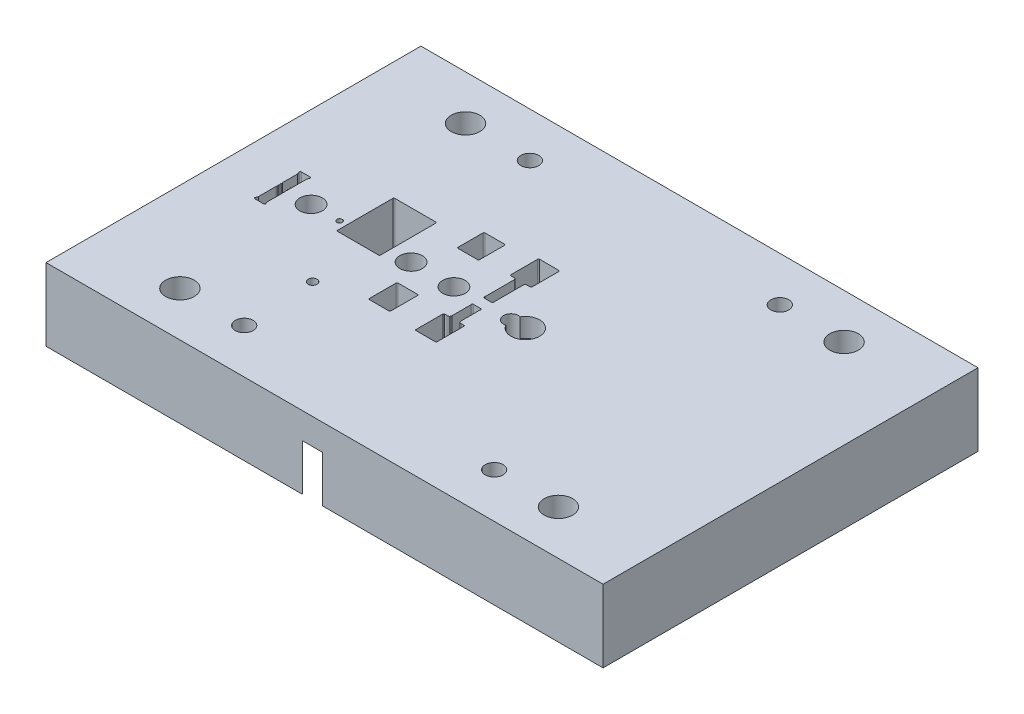
SolidWorks part; units mm, degrees
ref_plane "Front" through (0, 0, 0) normal (0, 0, 1) x (1, 0, 0)
ref_plane "Top" through (0, 0, 0) normal (0, 1, 0) x (1, 0, 0)
ref_plane "Right" through (0, 0, 0) normal (1, 0, 0) x (0, 0, -1)
sketch "Sketch1" plane through (0, 0, 0) normal (0, 0, 1) x (1, 0, 0)
  line L1 (-78, 0) -> (78, 0)
  line L2 (-78, 0) -> (-78, 20.3)
  line L3 (-78, 20.3) -> (78, 20.3)
  line L4 (78, 0) -> (78, 20.3)
  dimension "D1" = 78
  dimension "D2" = 20.3
  dimension "D3" = 78
extrude "Extrude1" add sketch "Sketch1" along normal mid plane 105
hole_wizard "M6 Tapped Hole1" positions "Sketch3" profile "Sketch2" tap size "M6" standard "ISO" end condition through all
sketch "Sketch3" plane through (0, 20.3, 0) normal (0, 1, 0) x (-1, 0, 0)
  point P1 (35, -40)
  point P4 (-35, -40)
  point P13 (-35, 40)
  point P16 (35, 40)
sketch "Sketch2" plane through (-35, 20.3, -40) normal (1, 0, 0) x (0, 0, 1)
  line L0 (0, 0) -> (0, 20.3)
  line L1 (0, 20.3) -> (2.5, 20.3)
  line L2 (2.5, 20.3) -> (2.5, 0)
  line L5 (2.5, 0) -> (0, 0)
  line L11 (0, -6.35) -> (0, 107.95) construction
  dimension "Thru Tap Drill Dia." = 5
  dimension "Thru Tap Drill Depth" = 20.3
cosmetic thread "Hole Thread1" parameters "D2"=6
cosmetic thread "Hole Thread2" parameters "D2"=6
cosmetic thread "Hole Thread5" parameters "D2"=6
cosmetic thread "Hole Thread6" parameters "D2"=6
hole_wizard "Hole1" positions "Sketch5" profile "Sketch4" legacy end condition through all
sketch "Sketch5" plane through (0, 20.3, 0) normal (0, 1, 0) x (-1, 0, 0)
  point P1 (53, -40)
  point P4 (53, 40)
  point P7 (-53, -40)
  point P10 (-53, 40)
sketch "Sketch4" plane through (-53, 20.3, -40) normal (1, 0, 0) x (0, 0, 1)
  line L0 (0, 0) -> (0, 20.3)
  line L1 (0, 20.3) -> (4, 20.3)
  line L2 (4, 20.3) -> (4, 0)
  line L3 (4, 0) -> (0, 0)
  line L4 (0, 110) -> (0, -10) construction
  dimension "Diameter" = 8
  dimension "Depth" = 20.3
hole_wizard "Hole2" positions "Sketch7" profile "Sketch6" legacy
sketch "Sketch7" plane through (0, 0, 0) normal (0, -1, 0) x (1, 0, 0)
  point P0 (14, 14.65)
  point P3 (5, 12.15)
  point P6 (5, -12.1677)
  point P8 (14, -14.65)
  point P11 (35, -12.15)
  point P14 (35, 12.15)
  point P17 (44, 14.65)
  point P20 (44, -14.65)
sketch "Sketch6" plane through (14, 0, 14.65) normal (1, 0, 0) x (0, 0, -1)
  line L0 (0, 0) -> (0, 4.4)
  line L1 (0, 4.4) -> (3.5, 4.4)
  line L2 (3.5, 4.4) -> (3.5, 0)
  line L3 (3.5, 0) -> (0, 0)
  line L4 (0, 110) -> (0, -10) construction
  dimension "Diameter" = 7
  dimension "Depth" = 4.4
sketch "Sketch8" plane through (0, 0, 0) normal (0, -1, 0) x (1, 0, 0)
  line L0 (-78, 52.5) -> (-78, -52.5) construction
  line L1 (-78, 23) -> (-49, 23)
  line L2 (-78, 23) -> (-78, 5)
  line L3 (-78, 5) -> (-49, 5)
  line L4 (-46, 20) -> (-46, 8)
  line L5 (-75.2525, 6) -> (-50.7475, 6) construction
  line L6 (-78, -1) -> (-49, -1)
  line L7 (-78, -1) -> (-78, -21)
  line L8 (-78, -21) -> (-49, -21)
  line L9 (-46, -4) -> (-46, -18)
  line L10 (-78, 22) -> (-48, 22) construction
  line L11 (-76.6263, -2) -> (-49.3737, -2) construction
  line L13 (-78, -20) -> (-48, -20) construction
  line L14 (-48, 11) -> (-48, 22) construction
  arc A0 (-49, -21) -> (-46, -18) centre (-49, -18) ccw
  arc A1 (-49, -1) -> (-46, -4) centre (-49, -4) cw
  arc A2 (-49, 5) -> (-46, 8) centre (-49, 8) ccw
  arc A3 (-49, 23) -> (-46, 20) centre (-49, 20) cw
  dimension "D6" = 3
  dimension "D1" = 1
  dimension "D2" = 1
  dimension "D3" = 1
  dimension "D4" = 1
  dimension "D5" = 2
extrude "Cut-Extrude1" cut sketch "Sketch8" against normal blind 5
sketch "Sketch9" plane through (0, 20.3, 0) normal (0, 1, 0) x (1, 0, 0)
  line L0 (-9.965, 17.15) -> (-9.965, 9.65)
  line L1 (-9.7, 9.385) -> (-8.5894, 9.385)
  line L2 (-8.3917, 9.2771) -> (-8.3123, 9.1537)
  line L3 (-8.275, 9.0266) -> (-8.275, 0.7046)
  line L4 (-18.25, -8.1954) -> (-23.75, -8.1954)
  line L5 (-24, -8.4454) -> (-24, -15.9454)
  line L6 (-23.75, -16.1954) -> (-18.25, -16.1954)
  line L7 (-18, -15.9454) -> (-18, -8.4454)
  line L8 (-18.25, -8.1954) -> (-23.75, -8.1954) construction
  line L9 (-24, -8.4454) -> (-24, -15.9454) construction
  line L10 (-23.75, -16.1954) -> (-18.25, -16.1954) construction
  line L11 (-18, -15.9454) -> (-18, -8.4454) construction
  line L12 (-24, 15.9) -> (-24, 8.9)
  line L13 (-23.75, 8.65) -> (-18.25, 8.65)
  line L14 (-18, 8.9) -> (-18, 15.9)
  line L15 (-18.25, 16.15) -> (-23.75, 16.15)
  line L16 (-24, 15.9) -> (-24, 8.9) construction
  line L17 (-23.75, 8.65) -> (-18.25, 8.65) construction
  line L18 (-18, 8.9) -> (-18, 15.9) construction
  line L19 (-18.25, 16.15) -> (-23.75, 16.15) construction
  line L20 (-33.25, 11.9046) -> (-44.75, 11.9046)
  line L21 (-33, -3.8454) -> (-33, 11.6546)
  line L22 (-44.75, -4.0954) -> (-33.25, -4.0954)
  line L23 (-45, 11.6546) -> (-45, -3.8454)
  line L24 (-33.25, 11.9046) -> (-44.75, 11.9046) construction
  line L25 (-33, -3.8454) -> (-33, 11.6546) construction
  line L26 (-44.75, -4.0954) -> (-33.25, -4.0954) construction
  line L27 (-45, 11.6546) -> (-45, -3.8454) construction
  line L28 (-8.2892, 0.6243) -> (-8.299, 0.5972)
  line L29 (-8.05, 0.2416) -> (-5.95, 0.2416)
  line L30 (-63, -1.2694) -> (-60.1263, -1.2694) construction
  line L31 (-61.75, -6.7884) -> (-61.5151, -7.4339) construction
  line L32 (-64.25, -6.7884) -> (-64.4849, -7.4339) construction
  line L33 (-61.735, -6.7858) -> (-61.501, -7.4288)
  line L34 (-61.75, -7.7844) -> (-64.25, -7.7844)
  line L35 (-64.265, -6.7858) -> (-64.499, -7.4288)
  line L36 (-9, -9.1754) -> (-9.7, -9.1754)
  line L37 (-9.95, -9.4254) -> (-9.95, -16.9254)
  line L38 (-9.7, -17.1754) -> (-4.3, -17.1754)
  line L39 (-4.05, -16.9254) -> (-4.05, -9.4254)
  line L40 (-4.3, -9.1754) -> (-5, -9.1754)
  line L41 (-5.6073, -8.9669) -> (-5.7285, -8.582)
  line L42 (-5.74, -8.5069) -> (-5.74, -3.2709)
  line L43 (-5.7249, -3.1854) -> (-5.7051, -3.1309)
  line L44 (-5.94, -2.7954) -> (-8.06, -2.7954)
  line L45 (-8.2949, -3.1309) -> (-8.2751, -3.1854)
  line L46 (-8.26, -3.2709) -> (-8.26, -8.5069)
  line L47 (-8.2715, -8.582) -> (-8.3927, -8.9669)
  line L48 (-9, -9.1754) -> (-9.7, -9.1754) construction
  line L49 (-9.95, -9.4254) -> (-9.95, -16.9254) construction
  line L50 (-9.7, -17.1754) -> (-4.3, -17.1754) construction
  line L51 (-4.05, -16.9254) -> (-4.05, -9.4254) construction
  line L52 (-4.3, -9.1754) -> (-5, -9.1754) construction
  line L53 (-5.6073, -8.9669) -> (-5.7285, -8.582) construction
  line L54 (-5.74, -8.5069) -> (-5.74, -3.2709) construction
  line L55 (-5.7249, -3.1854) -> (-5.7051, -3.1309) construction
  line L56 (-5.94, -2.7954) -> (-8.06, -2.7954) construction
  line L57 (-8.2949, -3.1309) -> (-8.2751, -3.1854) construction
  line L58 (-8.26, -3.2709) -> (-8.26, -8.5069) construction
  line L59 (-8.2715, -8.582) -> (-8.3927, -8.9669) construction
  line L60 (-9.95, 17.15) -> (-9.95, 9.65)
  line L61 (-9.7, 9.4) -> (-8.5894, 9.4)
  line L62 (-8.3791, 9.2852) -> (-8.2997, 9.1618)
  line L63 (-8.26, 9.0266) -> (-8.26, 0.7046)
  line L64 (-8.2751, 0.6191) -> (-8.2849, 0.5921)
  line L65 (-8.05, 0.2566) -> (-5.95, 0.2566)
  line L66 (-5.7151, 0.5921) -> (-5.7249, 0.6191)
  line L67 (-5.74, 0.7046) -> (-5.74, 9.0266)
  line L68 (-5.7003, 9.1618) -> (-5.6209, 9.2852)
  line L69 (-5.4106, 9.4) -> (-4.3, 9.4)
  line L70 (-4.05, 9.65) -> (-4.05, 17.15)
  line L71 (-4.3, 17.4) -> (-9.7, 17.4)
  line L72 (-9.95, 17.15) -> (-9.95, 9.65) construction
  line L73 (-9.7, 9.4) -> (-8.5894, 9.4) construction
  line L74 (-8.3791, 9.2852) -> (-8.2997, 9.1618) construction
  line L75 (-8.26, 9.0266) -> (-8.26, 0.7046) construction
  line L76 (-8.2751, 0.6191) -> (-8.2849, 0.5921) construction
  line L77 (-8.05, 0.2566) -> (-5.95, 0.2566) construction
  line L78 (-5.7151, 0.5921) -> (-5.7249, 0.6191) construction
  line L79 (-5.74, 0.7046) -> (-5.74, 9.0266) construction
  line L80 (-5.7003, 9.1618) -> (-5.6209, 9.2852) construction
  line L81 (-5.4106, 9.4) -> (-4.3, 9.4) construction
  line L82 (-4.05, 9.65) -> (-4.05, 17.15) construction
  line L83 (-4.3, 17.4) -> (-9.7, 17.4) construction
  line L84 (-64.265, -1.7954) -> (-64.265, -6.7858)
  line L85 (-64.265, 4.247) -> (-64.265, 0.0046)
  line L86 (-64.265, 4.247) -> (-64.499, 4.89)
  line L87 (-64.25, 5.2456) -> (-61.75, 5.2456)
  line L88 (-61.735, 4.247) -> (-61.501, 4.89)
  line L89 (-61.735, 0.0046) -> (-61.735, 4.247)
  line L90 (-5.701, 0.5972) -> (-5.7108, 0.6243)
  line L91 (-5.725, 0.7046) -> (-5.725, 9.0266)
  line L92 (-5.6877, 9.1537) -> (-5.6083, 9.2771)
  line L93 (-5.4106, 9.385) -> (-4.3, 9.385)
  line L94 (-4.035, 9.65) -> (-4.035, 17.15)
  line L95 (-4.3, 17.415) -> (-9.7, 17.415)
  line L96 (-61.735, -6.7858) -> (-61.735, -1.7954)
  line L114 (-64.25, 7.2306) -> (-64.25, 0.0046) construction
  line L115 (-61.75, 0.0046) -> (-61.75, 7.2306) construction
  line L116 (-64.25, -1.7954) -> (-64.25, -9.7694) construction
  line L117 (-61.75, -9.7694) -> (-61.75, -1.7954) construction
  line L118 (-61.75, -7.7694) -> (-64.25, -7.7694) construction
  line L119 (-64.25, 5.2306) -> (-61.75, 5.2306) construction
  line L120 (-64.25, 4.2497) -> (-64.25, 0.0046) construction
  line L121 (-61.75, 0.0046) -> (-61.75, 4.2497) construction
  line L122 (-64.25, -1.7954) -> (-64.25, -6.7884) construction
  line L123 (-61.75, -6.7884) -> (-61.75, -1.7954) construction
  line L124 (-61.75, -7.7694) -> (-64.25, -7.7694) construction
  line L125 (-64.25, 5.2306) -> (-61.75, 5.2306) construction
  line L126 (-64.25, 4.2497) -> (-64.4849, 4.8951) construction
  line L127 (-64.25, 3.4217) -> (-61.75, 3.4217) construction
  line L128 (-63, 3.4217) -> (-63, 4.4835) construction
  line L129 (-61.75, 4.2497) -> (-61.5151, 4.8951) construction
  line L130 (-63, -7.7694) -> (-63, 5.2306) construction
  line L138 (-9, -9.1604) -> (-9.7, -9.1604)
  line L139 (-9.965, -9.4254) -> (-9.965, -16.9254)
  line L140 (-9.7, -17.1904) -> (-4.3, -17.1904)
  line L141 (-4.035, -16.9254) -> (-4.035, -9.4254)
  line L142 (-4.3, -9.1604) -> (-5, -9.1604)
  line L143 (-5.593, -8.9624) -> (-5.7142, -8.5775)
  line L144 (-5.725, -8.5069) -> (-5.725, -3.2709)
  line L145 (-5.7108, -3.1905) -> (-5.691, -3.136)
  line L146 (-5.94, -2.7804) -> (-8.06, -2.7804)
  line L147 (-8.309, -3.136) -> (-8.2892, -3.1905)
  line L148 (-8.275, -3.2709) -> (-8.275, -8.5069)
  line L149 (-8.2858, -8.5775) -> (-8.407, -8.9624)
  line L150 (-24.015, 15.9) -> (-24.015, 8.9)
  line L151 (-23.75, 8.635) -> (-18.25, 8.635)
  line L152 (-17.985, 8.9) -> (-17.985, 15.9)
  line L153 (-18.25, 16.165) -> (-23.75, 16.165)
  line L154 (-18.25, -8.1804) -> (-23.75, -8.1804)
  line L155 (-24.015, -8.4454) -> (-24.015, -15.9454)
  line L156 (-23.75, -16.2104) -> (-18.25, -16.2104)
  line L157 (-17.985, -15.9454) -> (-17.985, -8.4454)
  line L158 (-33.25, 11.9196) -> (-44.75, 11.9196)
  line L159 (-45.015, 11.6546) -> (-45.015, -3.8454)
  line L160 (-44.75, -4.1104) -> (-33.25, -4.1104)
  line L161 (-32.985, -3.8454) -> (-32.985, 11.6546)
  arc A0 (-9.965, 9.65) -> (-9.7, 9.385) centre (-9.7, 9.65) ccw
  arc A1 (-8.3917, 9.2771) -> (-8.5894, 9.385) centre (-8.5894, 9.15) ccw
  arc A2 (-8.275, 9.0266) -> (-8.3123, 9.1537) centre (-8.51, 9.0266) ccw
  arc A3 (-8.2892, 0.6243) -> (-8.275, 0.7046) centre (-8.51, 0.7046) ccw
  arc A4 (-23.75, -8.1954) -> (-24, -8.4454) centre (-23.75, -8.4454) ccw
  arc A5 (-24, -15.9454) -> (-23.75, -16.1954) centre (-23.75, -15.9454) ccw
  arc A6 (-18.25, -16.1954) -> (-18, -15.9454) centre (-18.25, -15.9454) ccw
  arc A7 (-18, -8.4454) -> (-18.25, -8.1954) centre (-18.25, -8.4454) ccw
  arc A8 (-23.75, -8.1954) -> (-24, -8.4454) centre (-23.75, -8.4454) ccw construction
  arc A9 (-24, -15.9454) -> (-23.75, -16.1954) centre (-23.75, -15.9454) ccw construction
  arc A10 (-18.25, -16.1954) -> (-18, -15.9454) centre (-18.25, -15.9454) ccw construction
  arc A11 (-18, -8.4454) -> (-18.25, -8.1954) centre (-18.25, -8.4454) ccw construction
  arc A12 (-24, 8.9) -> (-23.75, 8.65) centre (-23.75, 8.9) ccw
  arc A13 (-18.25, 8.65) -> (-18, 8.9) centre (-18.25, 8.9) ccw
  arc A14 (-18, 15.9) -> (-18.25, 16.15) centre (-18.25, 15.9) ccw
  arc A15 (-23.75, 16.15) -> (-24, 15.9) centre (-23.75, 15.9) ccw
  arc A16 (-24, 8.9) -> (-23.75, 8.65) centre (-23.75, 8.9) ccw construction
  arc A17 (-18.25, 8.65) -> (-18, 8.9) centre (-18.25, 8.9) ccw construction
  arc A18 (-18, 15.9) -> (-18.25, 16.15) centre (-18.25, 15.9) ccw construction
  arc A19 (-23.75, 16.15) -> (-24, 15.9) centre (-23.75, 15.9) ccw construction
  arc A20 (-33, 11.6546) -> (-33.25, 11.9046) centre (-33.25, 11.6546) ccw
  arc A21 (-33.25, -4.0954) -> (-33, -3.8454) centre (-33.25, -3.8454) ccw
  arc A22 (-45, -3.8454) -> (-44.75, -4.0954) centre (-44.75, -3.8454) ccw
  arc A23 (-44.75, 11.9046) -> (-45, 11.6546) centre (-44.75, 11.6546) ccw
  arc A24 (-33, 11.6546) -> (-33.25, 11.9046) centre (-33.25, 11.6546) ccw construction
  arc A25 (-33.25, -4.0954) -> (-33, -3.8454) centre (-33.25, -3.8454) ccw construction
  arc A26 (-45, -3.8454) -> (-44.75, -4.0954) centre (-44.75, -3.8454) ccw construction
  arc A27 (-44.75, 11.9046) -> (-45, 11.6546) centre (-44.75, 11.6546) ccw construction
  arc A28 (-8.299, 0.5972) -> (-8.05, 0.2416) centre (-8.05, 0.5066) ccw
  arc A29 (-5.95, 0.2416) -> (-5.701, 0.5972) centre (-5.95, 0.5066) ccw
  arc A30 (-5.725, 0.7046) -> (-5.7108, 0.6243) centre (-5.49, 0.7046) ccw
  arc A31 (-5.6877, 9.1537) -> (-5.725, 9.0266) centre (-5.49, 9.0266) ccw
  arc A32 (-5.4106, 9.385) -> (-5.6083, 9.2771) centre (-5.4106, 9.15) ccw
  arc A33 (-4.3, 9.385) -> (-4.035, 9.65) centre (-4.3, 9.65) ccw
  arc A34 (-4.035, 17.15) -> (-4.3, 17.415) centre (-4.3, 17.15) ccw
  arc A35 (-9.7, 17.415) -> (-9.965, 17.15) centre (-9.7, 17.15) ccw
  arc A36 (-9.95, 9.65) -> (-9.7, 9.4) centre (-9.7, 9.65) ccw
  arc A37 (-8.3791, 9.2852) -> (-8.5894, 9.4) centre (-8.5894, 9.15) ccw
  arc A38 (-8.26, 9.0266) -> (-8.2997, 9.1618) centre (-8.51, 9.0266) ccw
  arc A39 (-8.2751, 0.6191) -> (-8.26, 0.7046) centre (-8.51, 0.7046) ccw
  arc A40 (-8.5194, -9.0963) -> (-8.4688, -9.0707) centre (-8.5835, -8.9068) ccw
  arc A41 (-9, -9.1754) -> (-8.5194, -9.0963) centre (-9, -7.6754) ccw
  arc A42 (-9.7, -9.1754) -> (-9.95, -9.4254) centre (-9.7, -9.4254) ccw
  arc A43 (-9.95, -16.9254) -> (-9.7, -17.1754) centre (-9.7, -16.9254) ccw
  arc A44 (-4.3, -17.1754) -> (-4.05, -16.9254) centre (-4.3, -16.9254) ccw
  arc A45 (-4.05, -9.4254) -> (-4.3, -9.1754) centre (-4.3, -9.4254) ccw
  arc A46 (-5.4806, -9.0963) -> (-5, -9.1754) centre (-5, -7.6754) ccw
  arc A47 (-5.5312, -9.0707) -> (-5.4806, -9.0963) centre (-5.4165, -8.9068) ccw
  arc A48 (-5.6073, -8.9669) -> (-5.5312, -9.0707) centre (-5.4165, -8.9068) ccw
  arc A49 (-5.74, -8.5069) -> (-5.7285, -8.582) centre (-5.49, -8.5069) ccw
  arc A50 (-5.7249, -3.1854) -> (-5.74, -3.2709) centre (-5.49, -3.2709) ccw
  arc A51 (-5.7051, -3.1309) -> (-5.94, -2.7954) centre (-5.94, -3.0454) ccw
  arc A52 (-8.06, -2.7954) -> (-8.2949, -3.1309) centre (-8.06, -3.0454) ccw
  arc A53 (-8.26, -3.2709) -> (-8.2751, -3.1854) centre (-8.51, -3.2709) ccw
  arc A54 (-8.2715, -8.582) -> (-8.26, -8.5069) centre (-8.51, -8.5069) ccw
  arc A55 (-8.4688, -9.0707) -> (-8.3927, -8.9669) centre (-8.5835, -8.9068) ccw
  arc A56 (-8.5194, -9.0963) -> (-8.4688, -9.0707) centre (-8.5835, -8.9068) ccw construction
  arc A57 (-9, -9.1754) -> (-8.5194, -9.0963) centre (-9, -7.6754) ccw construction
  arc A58 (-9.7, -9.1754) -> (-9.95, -9.4254) centre (-9.7, -9.4254) ccw construction
  arc A59 (-9.95, -16.9254) -> (-9.7, -17.1754) centre (-9.7, -16.9254) ccw construction
  arc A60 (-4.3, -17.1754) -> (-4.05, -16.9254) centre (-4.3, -16.9254) ccw construction
  arc A61 (-4.05, -9.4254) -> (-4.3, -9.1754) centre (-4.3, -9.4254) ccw construction
  arc A62 (-5.4806, -9.0963) -> (-5, -9.1754) centre (-5, -7.6754) ccw construction
  arc A63 (-5.5312, -9.0707) -> (-5.4806, -9.0963) centre (-5.4165, -8.9068) ccw construction
  arc A64 (-5.6073, -8.9669) -> (-5.5312, -9.0707) centre (-5.4165, -8.9068) ccw construction
  arc A65 (-5.74, -8.5069) -> (-5.7285, -8.582) centre (-5.49, -8.5069) ccw construction
  arc A66 (-5.7249, -3.1854) -> (-5.74, -3.2709) centre (-5.49, -3.2709) ccw construction
  arc A67 (-5.7051, -3.1309) -> (-5.94, -2.7954) centre (-5.94, -3.0454) ccw construction
  arc A68 (-8.06, -2.7954) -> (-8.2949, -3.1309) centre (-8.06, -3.0454) ccw construction
  arc A69 (-8.26, -3.2709) -> (-8.2751, -3.1854) centre (-8.51, -3.2709) ccw construction
  arc A70 (-8.2715, -8.582) -> (-8.26, -8.5069) centre (-8.51, -8.5069) ccw construction
  arc A71 (-8.4688, -9.0707) -> (-8.3927, -8.9669) centre (-8.5835, -8.9068) ccw construction
  arc A72 (-8.2849, 0.5921) -> (-8.05, 0.2566) centre (-8.05, 0.5066) ccw
  arc A73 (-5.95, 0.2566) -> (-5.7151, 0.5921) centre (-5.95, 0.5066) ccw
  arc A74 (-5.74, 0.7046) -> (-5.7249, 0.6191) centre (-5.49, 0.7046) ccw
  arc A75 (-5.7003, 9.1618) -> (-5.74, 9.0266) centre (-5.49, 9.0266) ccw
  arc A76 (-5.4106, 9.4) -> (-5.6209, 9.2852) centre (-5.4106, 9.15) ccw
  arc A77 (-4.3, 9.4) -> (-4.05, 9.65) centre (-4.3, 9.65) ccw
  arc A78 (-4.05, 17.15) -> (-4.3, 17.4) centre (-4.3, 17.15) ccw
  arc A79 (-9.7, 17.4) -> (-9.95, 17.15) centre (-9.7, 17.15) ccw
  arc A80 (-9.95, 9.65) -> (-9.7, 9.4) centre (-9.7, 9.65) ccw construction
  arc A81 (-8.3791, 9.2852) -> (-8.5894, 9.4) centre (-8.5894, 9.15) ccw construction
  arc A82 (-8.26, 9.0266) -> (-8.2997, 9.1618) centre (-8.51, 9.0266) ccw construction
  arc A83 (-8.2751, 0.6191) -> (-8.26, 0.7046) centre (-8.51, 0.7046) ccw construction
  arc A84 (-8.2849, 0.5921) -> (-8.05, 0.2566) centre (-8.05, 0.5066) ccw construction
  arc A85 (-5.95, 0.2566) -> (-5.7151, 0.5921) centre (-5.95, 0.5066) ccw construction
  arc A86 (-5.74, 0.7046) -> (-5.7249, 0.6191) centre (-5.49, 0.7046) ccw construction
  arc A87 (-5.7003, 9.1618) -> (-5.74, 9.0266) centre (-5.49, 9.0266) ccw construction
  arc A88 (-5.4106, 9.4) -> (-5.6209, 9.2852) centre (-5.4106, 9.15) ccw construction
  arc A89 (-4.3, 9.4) -> (-4.05, 9.65) centre (-4.3, 9.65) ccw construction
  arc A90 (-4.05, 17.15) -> (-4.3, 17.4) centre (-4.3, 17.15) ccw construction
  arc A91 (-9.7, 17.4) -> (-9.95, 17.15) centre (-9.7, 17.15) ccw construction
  arc A92 (-61.5151, -7.4339) -> (-61.75, -7.7694) centre (-61.75, -7.5194) cw construction
  arc A93 (-64.4849, -7.4339) -> (-64.25, -7.7694) centre (-64.25, -7.5194) ccw construction
  arc A94 (-61.501, -7.4288) -> (-61.75, -7.7844) centre (-61.75, -7.5194) cw
  arc A95 (-64.499, -7.4288) -> (-64.25, -7.7844) centre (-64.25, -7.5194) ccw
  arc A96 (-64.212, -1.6364) -> (-64.265, -1.7954) centre (-64, -1.7954) ccw
  arc A97 (-64.212, -1.6364) -> (-64.212, -1.3544) centre (-64.4, -1.4954) ccw
  arc A98 (-64.212, -1.0364) -> (-64.212, -1.3544) centre (-64, -1.1954) ccw
  arc A99 (-64.212, -1.0364) -> (-64.212, -0.7544) centre (-64.4, -0.8954) ccw
  arc A100 (-64.212, -0.4364) -> (-64.212, -0.7544) centre (-64, -0.5954) ccw
  arc A101 (-64.212, -0.4364) -> (-64.212, -0.1544) centre (-64.4, -0.2954) ccw
  arc A102 (-64.265, 0.0046) -> (-64.212, -0.1544) centre (-64, 0.0046) ccw
  arc A103 (-64.499, 4.89) -> (-64.25, 5.2456) centre (-64.25, 4.9806) cw
  arc A104 (-61.501, 4.89) -> (-61.75, 5.2456) centre (-61.75, 4.9806) ccw
  arc A105 (-61.788, -0.1544) -> (-61.735, 0.0046) centre (-62, 0.0046) ccw
  arc A106 (-61.788, -0.1544) -> (-61.788, -0.4364) centre (-61.6, -0.2954) ccw
  arc A107 (-61.788, -0.7544) -> (-61.788, -0.4364) centre (-62, -0.5954) ccw
  arc A108 (-61.788, -0.7544) -> (-61.788, -1.0364) centre (-61.6, -0.8954) ccw
  arc A109 (-61.788, -1.3544) -> (-61.788, -1.0364) centre (-62, -1.1954) ccw
  arc A110 (-61.788, -1.3544) -> (-61.788, -1.6364) centre (-61.6, -1.4954) ccw
  arc A111 (-61.735, -1.7954) -> (-61.788, -1.6364) centre (-62, -1.7954) ccw
  arc A132 (-61.8, -0.1454) -> (-61.75, 0.0046) centre (-62, 0.0046) ccw construction
  arc A133 (-61.8, -0.1454) -> (-61.8, -0.4454) centre (-61.6, -0.2954) ccw construction
  arc A134 (-61.8, -0.7454) -> (-61.8, -0.4454) centre (-62, -0.5954) ccw construction
  arc A135 (-61.8, -0.7454) -> (-61.8, -1.0454) centre (-61.6, -0.8954) ccw construction
  arc A136 (-61.8, -1.3454) -> (-61.8, -1.0454) centre (-62, -1.1954) ccw construction
  arc A137 (-61.8, -1.3454) -> (-61.8, -1.6454) centre (-61.6, -1.4954) ccw construction
  arc A138 (-61.75, -1.7954) -> (-61.8, -1.6454) centre (-62, -1.7954) ccw construction
  arc A139 (-61.8, -0.1454) -> (-61.75, 0.0046) centre (-62, 0.0046) ccw construction
  arc A140 (-61.8, -0.1454) -> (-61.8, -0.4454) centre (-61.6, -0.2954) ccw construction
  arc A141 (-61.8, -0.7454) -> (-61.8, -0.4454) centre (-62, -0.5954) ccw construction
  arc A142 (-61.8, -0.7454) -> (-61.8, -1.0454) centre (-61.6, -0.8954) ccw construction
  arc A143 (-61.8, -1.3454) -> (-61.8, -1.0454) centre (-62, -1.1954) ccw construction
  arc A144 (-61.8, -1.3454) -> (-61.8, -1.6454) centre (-61.6, -1.4954) ccw construction
  arc A145 (-61.75, -1.7954) -> (-61.8, -1.6454) centre (-62, -1.7954) ccw construction
  arc A146 (-64.25, 0.0046) -> (-64.2, -0.1454) centre (-64, 0.0046) ccw construction
  arc A147 (-64.2, -0.4454) -> (-64.2, -0.1454) centre (-64.4, -0.2954) ccw construction
  arc A148 (-64.2, -0.4454) -> (-64.2, -0.7454) centre (-64, -0.5954) ccw construction
  arc A149 (-64.2, -1.0454) -> (-64.2, -0.7454) centre (-64.4, -0.8954) ccw construction
  arc A150 (-64.2, -1.0454) -> (-64.2, -1.3454) centre (-64, -1.1954) ccw construction
  arc A151 (-64.2, -1.6454) -> (-64.2, -1.3454) centre (-64.4, -1.4954) ccw construction
  arc A152 (-64.2, -1.6454) -> (-64.25, -1.7954) centre (-64, -1.7954) ccw construction
  arc A153 (-64.25, 0.0046) -> (-64.2, -0.1454) centre (-64, 0.0046) ccw construction
  arc A154 (-64.2, -0.4454) -> (-64.2, -0.1454) centre (-64.4, -0.2954) ccw construction
  arc A155 (-64.2, -0.4454) -> (-64.2, -0.7454) centre (-64, -0.5954) ccw construction
  arc A156 (-64.2, -1.0454) -> (-64.2, -0.7454) centre (-64.4, -0.8954) ccw construction
  arc A157 (-64.2, -1.0454) -> (-64.2, -1.3454) centre (-64, -1.1954) ccw construction
  arc A158 (-64.2, -1.6454) -> (-64.2, -1.3454) centre (-64.4, -1.4954) ccw construction
  arc A159 (-64.2, -1.6454) -> (-64.25, -1.7954) centre (-64, -1.7954) ccw construction
  arc A160 (-64.4849, 4.8951) -> (-64.25, 5.2306) centre (-64.25, 4.9806) cw construction
  arc A161 (-61.5151, 4.8951) -> (-61.75, 5.2306) centre (-61.75, 4.9806) ccw construction
  arc A186 (-9.7, -9.1604) -> (-9.965, -9.4254) centre (-9.7, -9.4254) ccw
  arc A187 (-9.965, -16.9254) -> (-9.7, -17.1904) centre (-9.7, -16.9254) ccw
  arc A188 (-4.3, -17.1904) -> (-4.035, -16.9254) centre (-4.3, -16.9254) ccw
  arc A189 (-4.035, -9.4254) -> (-4.3, -9.1604) centre (-4.3, -9.4254) ccw
  arc A190 (-5.4758, -9.0821) -> (-5, -9.1604) centre (-5, -7.6754) ccw
  arc A191 (-5.5226, -9.0584) -> (-5.4758, -9.0821) centre (-5.4165, -8.9068) ccw
  arc A192 (-5.593, -8.9624) -> (-5.5226, -9.0584) centre (-5.4165, -8.9068) ccw
  arc A193 (-5.725, -8.5069) -> (-5.7142, -8.5775) centre (-5.49, -8.5069) ccw
  arc A194 (-5.7108, -3.1905) -> (-5.725, -3.2709) centre (-5.49, -3.2709) ccw
  arc A195 (-5.691, -3.136) -> (-5.94, -2.7804) centre (-5.94, -3.0454) ccw
  arc A196 (-8.06, -2.7804) -> (-8.309, -3.136) centre (-8.06, -3.0454) ccw
  arc A197 (-8.275, -3.2709) -> (-8.2892, -3.1905) centre (-8.51, -3.2709) ccw
  arc A198 (-8.2858, -8.5775) -> (-8.275, -8.5069) centre (-8.51, -8.5069) ccw
  arc A199 (-8.4774, -9.0584) -> (-8.407, -8.9624) centre (-8.5835, -8.9068) ccw
  arc A200 (-8.5242, -9.0821) -> (-8.4774, -9.0584) centre (-8.5835, -8.9068) ccw
  arc A201 (-9, -9.1604) -> (-8.5242, -9.0821) centre (-9, -7.6754) ccw
  arc A202 (-24.015, 8.9) -> (-23.75, 8.635) centre (-23.75, 8.9) ccw
  arc A203 (-18.25, 8.635) -> (-17.985, 8.9) centre (-18.25, 8.9) ccw
  arc A204 (-17.985, 15.9) -> (-18.25, 16.165) centre (-18.25, 15.9) ccw
  arc A205 (-23.75, 16.165) -> (-24.015, 15.9) centre (-23.75, 15.9) ccw
  arc A206 (-23.75, -8.1804) -> (-24.015, -8.4454) centre (-23.75, -8.4454) ccw
  arc A207 (-24.015, -15.9454) -> (-23.75, -16.2104) centre (-23.75, -15.9454) ccw
  arc A208 (-18.25, -16.2104) -> (-17.985, -15.9454) centre (-18.25, -15.9454) ccw
  arc A209 (-17.985, -8.4454) -> (-18.25, -8.1804) centre (-18.25, -8.4454) ccw
  arc A210 (-44.75, 11.9196) -> (-45.015, 11.6546) centre (-44.75, 11.6546) ccw
  arc A211 (-45.015, -3.8454) -> (-44.75, -4.1104) centre (-44.75, -3.8454) ccw
  arc A212 (-33.25, -4.1104) -> (-32.985, -3.8454) centre (-33.25, -3.8454) ccw
  arc A213 (-32.985, 11.6546) -> (-33.25, 11.9196) centre (-33.25, 11.6546) ccw
  dimension "D12" = 0.25
  dimension "D6" = 20
  dimension "D1" = 0
  dimension "D2" = 0
  dimension "D3" = 0
  dimension "D4" = 0
  dimension "D5" = 0
  dimension "D7" = 0.015
  dimension "D8" = 0.015
  dimension "D9" = 0.015
  dimension "D10" = 0.015
  dimension "D11" = 0.015
  dimension "D13" = 0.015
extrude "Cut-Extrude2" cut sketch "Sketch9" against normal through all
hole_wizard "Hole3" positions "Sketch11" profile "Sketch10" legacy
sketch "Sketch11" plane through (0, 20.3, 0) normal (0, 1, 0) x (1, 0, 0)
  point P0 (1, -1.2694)
  point P3 (-15, -1.2694)
  point P6 (-27, -1.2694)
  point P9 (-55, -1.2694)
sketch "Sketch10" plane through (1, 20.3, 1.2694) normal (1, 0, 0) x (0, 0, 1)
  line L0 (0, 0) -> (0, 100)
  line L1 (0, 100) -> (1, 100)
  line L2 (1, 100) -> (1, 11.0392)
  line L3 (1, 11.0392) -> (1.6, 10)
  line L4 (1.6, 10) -> (1.6, 0)
  line L5 (1.6, 0) -> (0, 0)
  line L6 (0, -6.13) -> (0, 109.2824) construction
  line L7 (-1, 11.0392) -> (-1.6, 10) construction
  line L8 (0, 100) -> (-1, 100) construction
  dimension "Diameter" = 2
  dimension "Depth" = 100
  dimension "C-Drill Diameter" = 3.2
  dimension "C-Drill Depth" = 10
  dimension "C-Drill Angle" = 60
hole_wizard "Hole4" positions "Sketch13" profile "Sketch12" legacy
sketch "Sketch13" plane through (0, 20.3, 0) normal (0, 1, 0) x (1, 0, 0)
  point P0 (-15, -1.2694)
  point P3 (-27, -1.2694)
  point P6 (-55, -1.2694)
sketch "Sketch12" plane through (-15, 20.3, 1.2694) normal (1, 0, 0) x (0, 0, 1)
  line L0 (0, 0) -> (0, 10)
  line L1 (0, 10) -> (3.15, 10)
  line L2 (3.15, 10) -> (3.15, 0)
  line L3 (3.15, 0) -> (0, 0)
  line L4 (0, 110) -> (0, -10) construction
  dimension "Diameter" = 6.3
  dimension "Depth" = 10
hole_wizard "Hole6" positions "Sketch15" profile "Sketch14" legacy
sketch "Sketch15" plane through (0, 20.3, 0) normal (0, 1, 0) x (1, 0, 0)
  point P1 (1, -1.2694)
sketch "Sketch14" plane through (1, 20.3, 1.2694) normal (1, 0, 0) x (0, 0, 1)
  line L0 (0, 0) -> (0, 9.999)
  line L1 (0, 9.999) -> (2.1, 9.999)
  line L2 (2.1, 9.999) -> (2.1, 0)
  line L3 (2.1, 0) -> (0, 0)
  line L4 (0, 110) -> (0, -10) construction
  dimension "Diameter" = 4.2
  dimension "Depth" = 9.999
hole_wizard "Hole7" positions "Sketch17" profile "Sketch16" legacy end condition through all
sketch "Sketch17" plane through (0, 20.3, 0) normal (0, 1, 0) x (1, 0, 0)
  point P0 (5, -1.2694)
sketch "Sketch16" plane through (5, 20.3, 1.2694) normal (1, 0, 0) x (0, 0, 1)
  line L0 (0, 0) -> (0, 20.3)
  line L1 (0, 20.3) -> (1.015, 20.3)
  line L2 (1.015, 20.3) -> (1.015, 0)
  line L3 (1.015, 0) -> (0, 0)
  line L4 (0, 110) -> (0, -10) construction
  dimension "Diameter" = 2.03
  dimension "Depth" = 20.3
hole_wizard "Hole8" positions "Sketch19" profile "Sketch18" legacy end condition through all
sketch "Sketch19" plane through (0, 20.3, 0) normal (0, 1, 0) x (1, 0, 0)
  point P0 (-47, -1.2694)
sketch "Sketch18" plane through (-47, 20.3, 1.2694) normal (1, 0, 0) x (0, 0, 1)
  line L0 (0, 0) -> (0, 20.7506)
  line L1 (0, 20.7506) -> (0.75, 20.3)
  line L2 (0.75, 20.3) -> (0.75, 0)
  line L4 (0.75, 0) -> (0, 0)
  line L6 (0, 20.7506) -> (-0.75, 20.3) construction
  line L7 (0, -4.2442) -> (0, 117.3081) construction
  dimension "Diameter" = 1.5
  dimension "Depth" = 20.3
  dimension "Drill Angle" = 118
ref_plane "Plane1" through (78, 0, -52.5) normal (1, 0, 0) x (0, 0, -1)
sketch "Sketch21" plane through (0, 0, 0) normal (0, -1, 0) x (1, 0, 0)
  line L0 (-52.6533, 7.4489) -> (-26.8439, 33.2583) construction
  line L1 (-24.5391, 34.1347) -> (-3.1635, 55.5103) construction
  line L2 (-3.1635, 55.5103) -> (-0.335, 52.6819) construction
  line L3 (-0.335, 52.6819) -> (-21.7106, 31.3063) construction
  line L4 (-48.3965, 3.1921) -> (-22.5871, 29.0015) construction
  line L5 (-52.6533, 7.4489) -> (-26.8439, 33.2583)
  line L6 (-24.5391, 34.1347) -> (-3.1635, 55.5103)
  line L7 (-3.1635, 55.5103) -> (-0.335, 52.6819)
  line L8 (-0.335, 52.6819) -> (-21.7106, 31.3063)
  line L9 (-48.3965, 3.1921) -> (-22.5871, 29.0015)
  arc A0 (-24.5391, 34.1347) -> (-26.8439, 33.2583) centre (-24.7155, 31.1299) ccw construction
  arc A1 (-22.5871, 29.0015) -> (-21.7106, 31.3063) centre (-24.7155, 31.1299) ccw construction
  arc A2 (-52.6533, 7.4489) -> (-48.3965, 3.1921) centre (-50.5249, 5.3205) ccw construction
  arc A3 (-24.5391, 34.1347) -> (-26.8439, 33.2583) centre (-24.7155, 31.1299) ccw
  arc A4 (-22.5871, 29.0015) -> (-21.7106, 31.3063) centre (-24.7155, 31.1299) ccw
  arc A5 (-52.6533, 7.4489) -> (-48.3965, 3.1921) centre (-50.5249, 5.3205) ccw
extrude "Cut-Extrude3" cut sketch "Sketch21" against normal blind 13
sketch "Sketch23" plane through (0, 0, 0) normal (0, -1, 0) x (1, 0, 0)
  line L0 (-49, 23) -> (-37.1021, 23)
  line L1 (-26.8439, 33.2583) -> (-52.6533, 7.4489) construction
  line L2 (-37.1021, 23) -> (-46, 14.1021)
  line L3 (-46, 14.1021) -> (-49, 23)
extrude "Cut-Extrude4" cut sketch "Sketch23" against normal up to surface (5 mm away) up to face at (-60.4552, 5, 10.1599)
hole_wizard "M3 Tapped Hole1" positions "Sketch24" profile "Sketch25" tap size "M3" standard "ISO"
sketch "Sketch24" plane through (0, 13, 0) normal (0, -1, 0) x (-1, 0, 0)
  point P0 (36.0292, -19.8162)
sketch "Sketch25" plane through (-36.0292, 13, 19.8162) normal (1, 0, 0) x (0, 0, -1)
  line L0 (0, 0) -> (0, 8.2511)
  line L1 (0, 8.2511) -> (1.25, 7.5)
  line L2 (1.25, 7.5) -> (1.25, 0)
  line L5 (1.25, 0) -> (0, 0)
  line L10 (0, 8.2511) -> (-1.25, 7.5) construction
  line L11 (0, -6.35) -> (0, 107.95) construction
  dimension "Tap Drill Dia." = 2.5
  dimension "Tap Drill Depth" = 7.5
  dimension "Drill Angle" = 118
cosmetic thread "Hole Thread7" parameters "D1"=6, "D2"=3
sketch "Sketch26" plane through (0, 0, 0) normal (0, -1, 0) x (1, 0, 0)
  circle A0 centre (5, 1.2694) radius 2.5
  dimension "D1" = 5
extrude "Cut-Extrude5" cut sketch "Sketch26" against normal through all
sketch "Sketch27" plane through (0, 20.3, 0) normal (0, 1, 0) x (1, 0, 0)
  circle A0 centre (5, -1.2694) radius 4
  dimension "D1" = 8
extrude "Cut-Extrude6" cut sketch "Sketch27" against normal blind 5.3
equation "\"¸20\"=24.0852"
